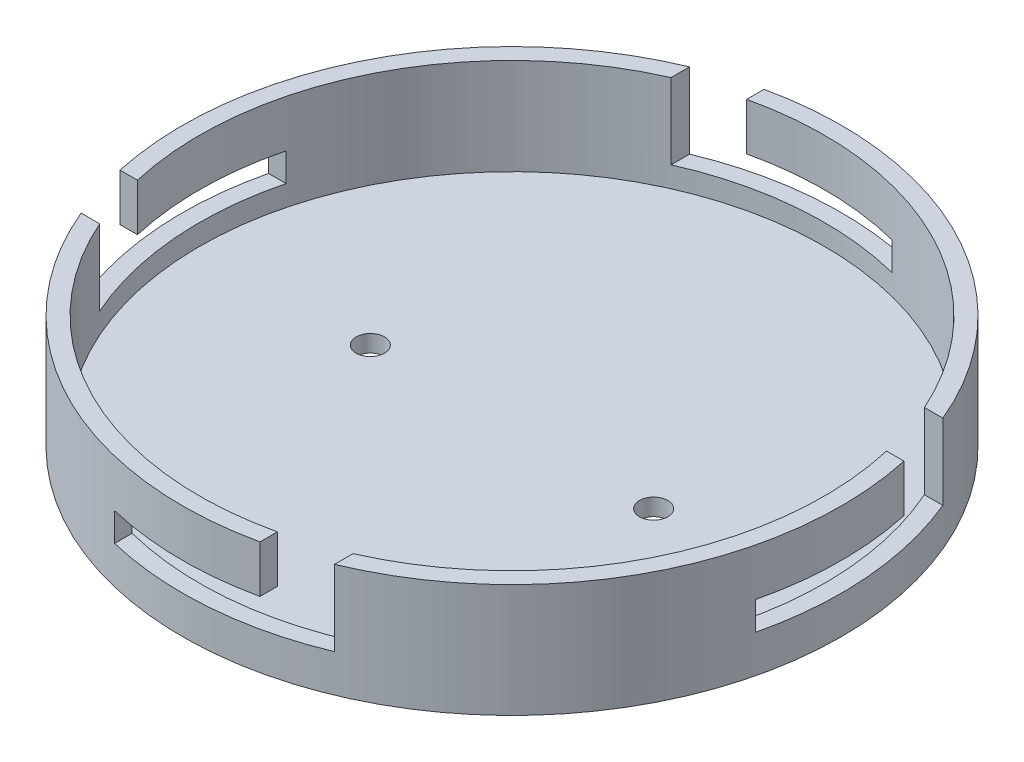
SolidWorks part; units mm, degrees
ref_plane "Ebene vorne" through (0, 0, 0) normal (0, 0, 1) x (1, 0, 0)
ref_plane "Ebene oben" through (0, 0, 0) normal (0, 1, 0) x (1, 0, 0)
ref_plane "Ebene rechts" through (0, 0, 0) normal (1, 0, 0) x (0, 0, -1)
sketch "Skizze1" plane through (0, 0, 0) normal (0, 1, 0) x (1, 0, 0)
  line L1 (-39, 39) -> (39, 39) construction
  line L2 (-39, 39) -> (-39, -39) construction
  line L3 (-39, -39) -> (39, -39) construction
  line L4 (39, 39) -> (39, -39) construction
  circle A0 centre (0, 0) radius 55.1543
  dimension "D1" = 78
extrude "Aufsatz-Linear austragen1" add sketch "Skizze1" along normal blind 3
extrude "Linear-Austragen-Dünn1" add sketch "Skizze1<2>" along normal blind 20 thin thin type one direction wall 3
sketch "Skizze1<2>" plane through (0, 0, 0) normal (0, 1, 0) x (1, 0, 0) same geometry as "Skizze1"
sketch "Skizze2" plane through (0, 0, 0) normal (1, 0, 0) x (0, 0, -1)
  line L0 (58.1543, 20) -> (-58.1543, 20) construction
  line L1 (-22.3498, 20) -> (-12.3498, 20)
  line L2 (-22.3498, 20) -> (-22.3498, 6.6585)
  line L3 (-22.3498, 6.6585) -> (-12.3498, 6.6585)
  line L4 (-12.3498, 20) -> (-12.3498, 6.6585)
  line L6 (-12.3498, 6.6585) -> (13.5852, 6.6585)
  line L7 (-12.3498, 6.6585) -> (-12.3498, 11.6585)
  line L8 (-12.3498, 11.6585) -> (13.5852, 11.6585)
  line L9 (13.5852, 6.6585) -> (13.5852, 11.6585)
  dimension "D1" = 10
  dimension "D2" = 5
extrude "Schnitt-Linear austragen1" cut sketch "Skizze2" against normal through all contours L4 L1 L2 L3 | L6 L9 L8 L4 region at (0, 13.3292, 17.3498) region at (0, 9.1585, -0.6177)
pattern_circular "Kreismuster1" count 4 every 90 about axis through (0, 3, 0) along (0, -1, 0) of "Schnitt-Linear austragen1"
sketch "Skizze4" plane through (0, 3, 0) normal (0, 1, 0) x (1, 0, 0)
  circle A0 centre (-25, 0) radius 2.5
  circle A1 centre (25, 0) radius 2.5
  point P4 (0, 0)
  dimension "D3" = 5
  dimension "D1" = 25
  dimension "D2" = 25
extrude "Schnitt-Linear austragen5" cut sketch "Skizze4" against normal up to next
